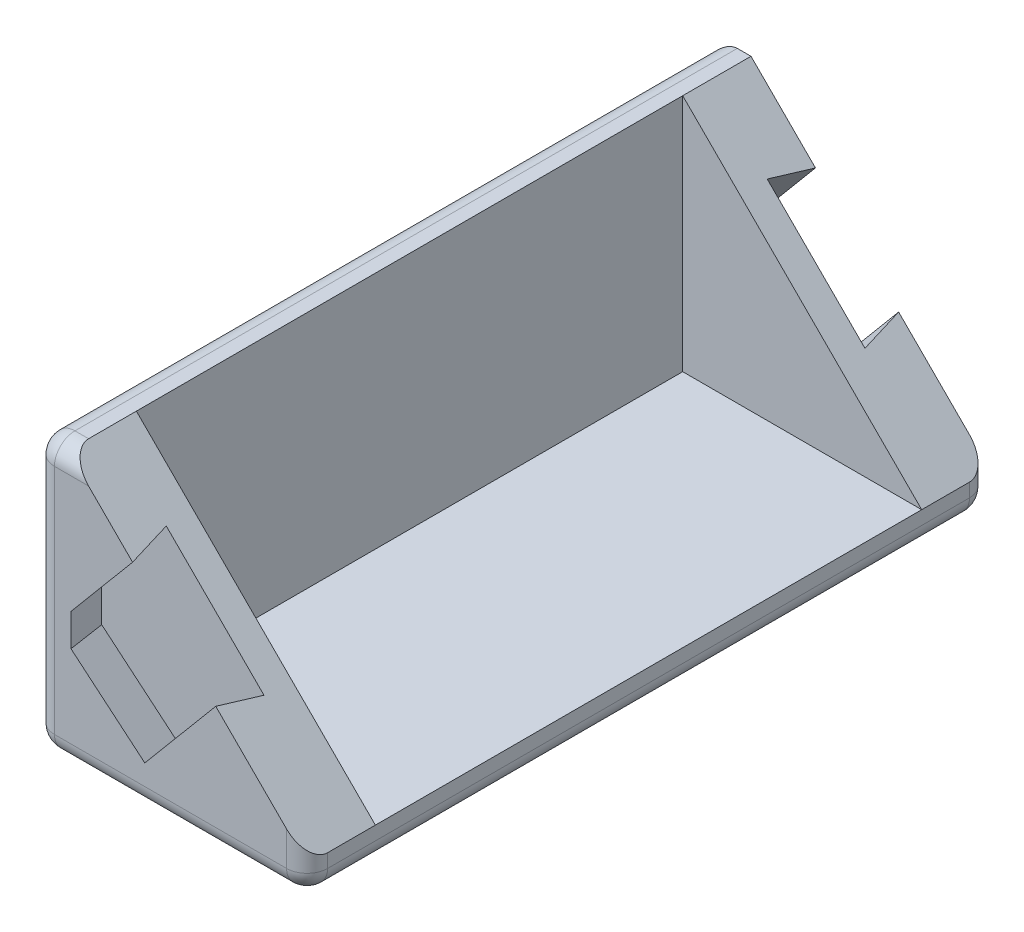
SolidWorks part; units mm, degrees
ref_plane "前视基准面" through (0, 0, 0) normal (0, 0, 1) x (1, 0, 0)
ref_plane "上视基准面" through (0, 0, 0) normal (0, 1, 0) x (1, 0, 0)
ref_plane "右视基准面" through (0, 0, 0) normal (1, 0, 0) x (0, 0, -1)
sketch "草图1" plane through (0, 0, 0) normal (0, 0, 1) x (1, 0, 0)
  line L0 (0, 0) -> (-100, -119.1754)
  line L1 (-100, -119.1754) -> (-55, -119.1754)
  line L2 (100, -119.1754) -> (0, 0)
  line L3 (-100, -119.1754) -> (-100, -74.1754)
  line L4 (-100, -74.1754) -> (-55, -119.1754)
  line L6 (0, 0) -> (0, 50000) construction
  line L7 (0, 15.5572) -> (-96, -98.8511)
  line L8 (-10.5203, -28.0949) -> (-83.5895, -115.1754)
  line L9 (7.6604, -6.4279) -> (-92.3396, -125.6032) construction
  line L10 (-7.6604, 6.4279) -> (-107.6604, -112.7475) construction
  line L13 (0, 0) -> (-42.5357, 0) construction
  line L14 (0, -119.1754) -> (100, -119.1754)
  line L21 (-96, -104.7617) -> (-83.5895, -115.1754)
  line L22 (-96, -119.1754) -> (-96, -88.5856) construction
  line L23 (-96, -98.8511) -> (-96, -104.7617)
  line L24 (1.1491, 14.5931) -> (-94.5, -99.3971)
  line L25 (-94.5, -99.3971) -> (-94.5, -104.0623)
  line L26 (-94.5, -104.0623) -> (-83.7744, -113.0621)
  line L27 (-11.6694, -27.1307) -> (-83.7744, -113.0621)
  line L28 (-81.6478, -81.7469) -> (-66.327, -94.6026)
  circle A0 centre (0, 0) radius 4
  circle A1 centre (0, 0) radius 11.15
  circle A2 centre (0, 0) radius 30
  dimension "D4" = 8
  dimension "D11" = 22.3
  dimension "D12" = 60
  dimension "D1" = 200
  dimension "D2" = 50
  dimension "D3" = 45
  dimension "D7" = 45
  dimension "D8" = 4
  dimension "D9" = 4
  dimension "D10" = 1.5
  dimension "D5" = 10
  dimension "D6" = 10
sketch "草图3" plane through (0, 0, 0) normal (0, 0, 1) x (1, 0, 0)
  line L0 (-100, -119.1754) -> (-55, -119.1754) construction
  line L1 (-100, -74.1754) -> (-55, -119.1754) construction
  line L2 (-100, -119.1754) -> (-100, -74.1754) construction
  line L3 (-100, -119.1754) -> (-55, -119.1754)
  line L4 (-100, -74.1754) -> (-55, -119.1754)
  line L5 (-100, -119.1754) -> (-100, -74.1754)
  line L6 (-100, -79.1754) -> (-95, -79.1754)
  line L7 (-60, -114.1754) -> (-60, -119.1754)
  dimension "D1" = 5
  dimension "D2" = 5
extrude "凸台-拉伸1" add sketch "草图3" against normal blind 10 contours L7 L4 L6 L5 L3
sketch "草图8" plane through (0, 0, 0) normal (0, 0, 1) x (1, 0, 0)
  line L46 (-81.6478, -81.7469) -> (-66.327, -94.6026) construction
  line L47 (-80.5601, -82.6596) -> (-67.4147, -93.6899)
  line L50 (-94.58, -99.3679) -> (1.0878, 14.6445)
  line L56 (-11.6081, -27.1821) -> (-83.7646, -113.1748)
  line L57 (-83.7646, -113.1748) -> (-94.58, -104.0996)
  line L58 (-94.58, -104.0996) -> (-94.58, -99.3679)
  line L59 (-94.58, -99.3679) -> (-80.5601, -82.6596)
  line L60 (-67.4147, -93.6899) -> (-83.7646, -113.1748)
  line L61 (-83.7646, -113.1748) -> (-94.58, -104.0996)
  line L62 (-94.58, -104.0996) -> (-94.58, -99.3679)
  dimension "D1" = 0.08
ref_plane "基准面1" through (0, 0, -6) normal (0, 0, 1) x (1, 0, 0)
sketch "草图5" plane through (0, 0, -6) normal (0, 0, 1) x (1, 0, 0)
  line L19 (-1.5366, 10.948) -> (0.8296, 14.9915)
  line L41 (-1.9367, 19.372) -> (0.4289, -30.4396)
  line L42 (-1.5366, 10.948) -> (0.8296, 14.9915)
  line L69 (-81.6478, -81.7469) -> (-66.327, -94.6026) construction
  line L70 (-81.7091, -81.6955) -> (-66.2657, -94.6541)
  line L71 (-1.6671, 13.6949) -> (-0.0613, 15.6087)
  line L73 (-96.08, -98.822) -> (-0.0613, 15.6087)
  line L74 (-10.4591, -28.1463) -> (-83.5797, -115.2881)
  line L75 (-83.5797, -115.2881) -> (-96.08, -104.799)
  line L76 (-96.08, -104.799) -> (-96.08, -98.822)
  line L77 (-96.08, -98.822) -> (-81.7091, -81.6955)
  line L78 (-66.2657, -94.6541) -> (-83.5797, -115.2881)
  line L79 (-83.5797, -115.2881) -> (-96.08, -104.799)
  line L80 (-96.08, -104.799) -> (-96.08, -98.822)
  dimension "D1" = 0.08
loft "切除-放样1" cut section "草图5" section "草图8" connector at (-96.08, -98.822, -6) connector at (-94.58, -99.3679, 0)
sketch "草图9" plane through (0, 0, -10) normal (0, 0, -1) x (-1, 0, 0)
  line L0 (100, -119.1754) -> (55, -119.1754) construction
  line L1 (100, -119.1754) -> (100, -74.1754) construction
  line L2 (100, -119.1754) -> (60, -119.1754)
  line L3 (100, -119.1754) -> (100, -79.1754)
  line L4 (95, -79.1754) -> (95, -114.1754)
  line L5 (60, -114.1754) -> (60, -119.1754)
  line L6 (60, -119.1754) -> (100, -119.1754)
  line L7 (100, -119.1754) -> (100, -79.1754)
  line L8 (100, -79.1754) -> (95, -79.1754)
  line L9 (95, -79.1754) -> (60, -114.1754)
  line L10 (60, -114.1754) -> (60, -119.1754)
  line L11 (60, -119.1754) -> (100, -119.1754)
  line L12 (100, -119.1754) -> (100, -79.1754)
  line L13 (100, -79.1754) -> (95, -79.1754)
  line L15 (95, -114.1754) -> (60, -114.1754)
  line M7 (60, -114.1754) -> (60, -119.1754)
  line M8 (60, -119.1754) -> (100, -119.1754)
  line M9 (100, -119.1754) -> (100, -79.1754)
  line M10 (100, -79.1754) -> (95, -79.1754)
  dimension "D1" = 0
extrude "凸台-拉伸3" add sketch "草图9" along normal blind 40 contours L4 L15 M7 M8 M9 M10
mirror "镜向2" about plane through (0, 0, -50) normal (0, 0, -1) of bodies 112
fillet "圆角2" radius 3 6 edges at (-60, -116.6754, -100) (-60, -116.6754, 0) (-100, -99.1754, -100) (-100, -99.1754, 0) (-100, -79.1754, -50) (-97.5, -79.1754, 0)
fillet "圆角3" radius 3 8 edges at (-99.1213, -119.1754, -0.8787) (-100, -119.1754, -50) (-99.1213, -119.1754, -99.1213) (-80, -119.1754, -100) (-60.8787, -119.1754, -99.1213) (-60, -119.1754, -50) (-60.8787, -119.1754, -0.8787) (-80, -119.1754, 0)
sketch "草图10" plane through (-100, 0, 0) normal (-1, 0, 0) x (0, 0, 1)
  line L0 (-51.5, -79.1754) -> (-51.5, -119.1754) construction
  line L1 (-100, -79.1754) -> (-3, -79.1754) construction
  line L2 (-3, -119.1754) -> (-97, -119.1754) construction
  line L3 (-90, -114.1754) -> (-10, -114.1754) construction
  line L5 (-29.85, -114.1754) -> (-29.85, -79.1754)
  line L7 (-73.15, -114.1754) -> (-73.15, -79.1754)
  line L8 (-51.5, -79.1754) -> (-51.5, -119.1754) construction
  line L9 (-29.85, -96.6754) -> (-73.15, -96.6754) construction
  line L10 (-73.15, -114.1754) -> (-29.85, -114.1754)
  line L11 (-73.15, -79.1754) -> (-29.85, -79.1754)
  point P6 (-51.5, -96.6754)
  dimension "D2" = 43.3
extrude "切除-拉伸1" [suppressed] cut sketch "草图10" against normal blind 12.8
sketch "草图11" [suppressed] plane through (0, -114.1754, 0) normal (0, 1, 0) x (1, 0, 0)
  line L0 (-83, 25.85) -> (-95, 25.85)
  line L1 (-60, 50) -> (-50060, 50) construction
  line L2 (-60, 90) -> (-60, 10) construction
  line L4 (-83, 77.15) -> (-83, 25.85)
  line L9 (-95, 29.85) -> (-95, 10) construction
  line L13 (-83, 77.15) -> (-95, 77.15)
  line L14 (-95, 90) -> (-95, 73.15) construction
  line L15 (-95, 77.15) -> (-95, 73.15)
  line L16 (-95, 29.85) -> (-95, 25.85)
  line L18 (-95, 73.15) -> (-87, 73.15)
  line L19 (-87, 73.15) -> (-87, 29.85)
  line L20 (-87, 29.85) -> (-95, 29.85)
  line L21 (-100, 73.15) -> (-100, 29.85) construction
  point P4 (-60, 50)
  dimension "D1" = 4
  dimension "D2" = 13
  dimension "D3" = 4
  dimension "D4" = 4
extrude "凸台-拉伸4" [suppressed] add sketch "草图11" along normal up to surface (35 mm away)
sketch "草图12" [suppressed] plane through (0, -79.1754, 0) normal (0, 1, 0) x (1, 0, 0)
  line L0 (-95, 77.15) -> (-83, 77.15) construction
  line L1 (-83, 25.85) -> (-100, 25.85)
  line L2 (-83, 25.85) -> (-83, 77.15)
  line L3 (-83, 77.15) -> (-100, 77.15)
  line L4 (-100, 25.85) -> (-100, 77.15)
  line L5 (-91.5, 77.15) -> (-91.5, 25.85) construction
  line L6 (-83, 51.5) -> (-100, 51.5) construction
  line L7 (-95, 25.85) -> (-83, 25.85) construction
  line L8 (-83, 77.15) -> (-83, 25.85) construction
  line L9 (-100, 73.15) -> (-100, 29.85) construction
  line L11 (-49.5567, -0.9458) -> (-111.1305, -0.9458)
  line L12 (-49.5567, -0.9458) -> (-49.5567, 103.9458)
  line L13 (-49.5567, 103.9458) -> (-111.1305, 103.9458)
  line L14 (-111.1305, -0.9458) -> (-111.1305, 103.9458)
  line L15 (-80.3436, 103.9458) -> (-80.3436, -0.9458) construction
  line L16 (-49.5567, 51.5) -> (-111.1305, 51.5) construction
  point P0 (-91.5, 51.5)
  point P15 (-80.3436, 51.5)
extrude "切除-拉伸2" [suppressed] cut sketch "草图12" against normal through all
ref_plane "基准面2" through (0, 0, -10) normal (0, 0, -1) x (-1, 0, 0)
other "使用曲面切除1"
